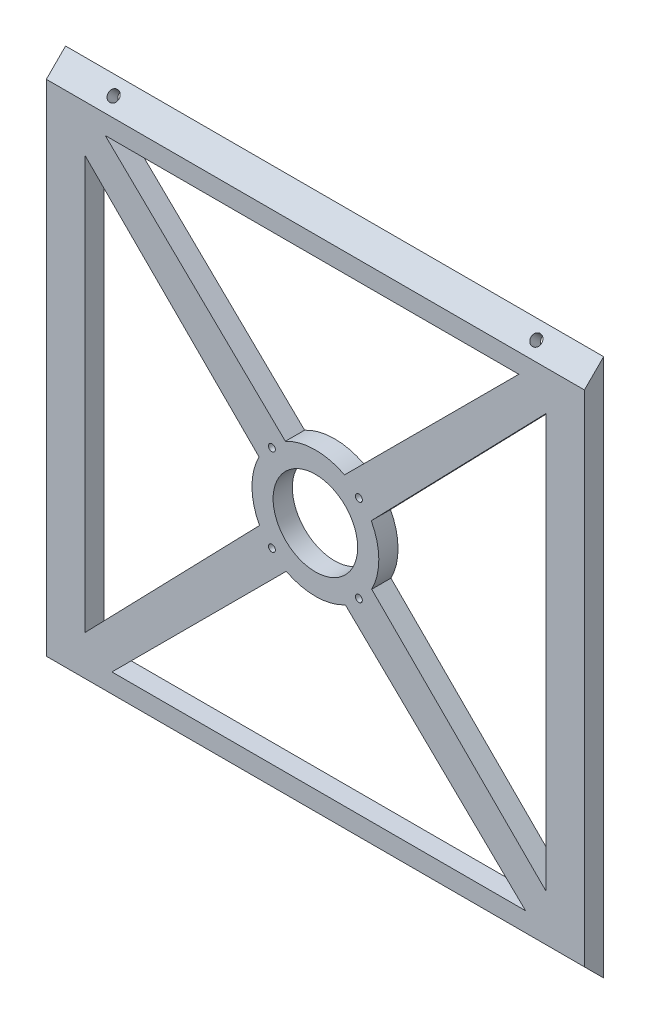
SolidWorks part; units mm, degrees
ref_plane "Front Plane" through (0, 0, 0) normal (0, 0, 1) x (1, 0, 0)
ref_plane "Top Plane" through (0, 0, 0) normal (0, 1, 0) x (1, 0, 0)
ref_plane "Right Plane" through (0, 0, 0) normal (1, 0, 0) x (0, 0, -1)
sketch "Sketch3" plane through (0, 0, 0) normal (0, 0, 1) x (1, 0, 0)
  line L1 (-70, 70) -> (70, 70)
  line L2 (-70, 70) -> (-70, -70)
  line L3 (-70, -70) -> (70, -70)
  line L4 (70, 70) -> (70, -70)
  line L5 (0, -70) -> (0, 70) construction
  line L6 (-70, 0) -> (70, 0) construction
  point P0 (0, 0)
  dimension "D1" = 140
  dimension "D2" = 140
extrude "Boss-Extrude1" add sketch "Sketch3" along normal blind 5
sketch "Sketch4" plane through (0, 0, 5) normal (0, 0, 1) x (1, 0, 0)
  line L0 (0, 0) -> (-70, 70) construction
  line L1 (0, 0) -> (70, 70) construction
  line L2 (-60, 60) -> (60, 60) construction
  line L3 (70, 70) -> (-70, 70) construction
  line L4 (-65, 70) -> (3.5355, 3.5355) construction
  line L5 (-3.5355, 3.5355) -> (52.9289, 60) construction
  line L6 (7.5831, 14.6542) -> (52.9289, 60)
  line L7 (-7.8076, 14.5359) -> (-54.6884, 60)
  line L8 (-54.6884, 60) -> (52.9289, 60)
  circle A0 centre (0, 0) radius 16.5 construction
  arc A1 (-7.8076, 14.5359) -> (7.5831, 14.6542) centre (0, 0) cw
  dimension "D1" = 33
  dimension "D2" = 10
  dimension "D3" = 10
  dimension "D4" = 5
  dimension "D5" = 5
  dimension "D6" = 5
extrude "Cut-Extrude1" cut sketch "Sketch4" against normal blind 5
pattern_circular "CirPattern1" count 4 over 360 about axis through (0, 0, 0) along (0, 0, 1) of "Cut-Extrude1"
sketch "Sketch7" plane through (0, 0, 5) normal (0, 0, 1) x (1, 0, 0)
  circle A0 centre (0, 0) radius 11
  dimension "D1" = 22
extrude "Cut-Extrude2" cut sketch "Sketch7" against normal up to next
sketch "Sketch8" plane through (0, 0, 5) normal (0, 0, 1) x (1, 0, 0)
  line L0 (0, 0) -> (70, -70) construction
  circle A0 centre (0, 0) radius 16 construction
  point P3 (11.3137, -11.3137)
  dimension "D1" = 32
hole_wizard "Ø1.8 (1.8) Diameter Hole1" positions "3DSketch3" profile "Sketch9" hole size "Ø1.8" standard "ANSI Metric"
sketch3d "3DSketch3"
  point P0 (11.3137, -11.3137, 5)
sketch "Sketch9" plane through (11.3137, -11.3137, 5) normal (1, 0, 0) x (0, -1, 0)
  line L0 (0, 0) -> (0, 6.5408)
  line L1 (0, 6.5408) -> (0.9, 6)
  line L2 (0.9, 6) -> (0.9, 0)
  line L5 (0.9, 0) -> (0, 0)
  line L10 (0, 6.5408) -> (-0.9, 6) construction
  line L11 (0, -6.35) -> (0, 107.95) construction
  dimension "Hole Dia." = 1.8
  dimension "Hole Depth" = 6
  dimension "Drill Angle" = 118
pattern_circular "CirPattern2" count 4 over 360 about axis through (0, 0, 0) along (0, 0, 1) of "Ø1.8 (1.8) Diameter Hole1"
chamfer "Chamfer1" distance 5 angle 45 2 edges at (0, 70, 5) (0, -70, 5)
hole_wizard "Ø3.0mm Dowel Hole1" positions "3DSketch5" profile "Sketch12" hole size "Ø3.0" standard "ANSI Metric"
sketch3d "3DSketch5"
  line L0 (-70, 70, 0) -> (-70, -70, 0) construction
  point P0 (-70, 63, 2.5)
  dimension "D1" = 2.5
  dimension "D2" = 63
sketch "Sketch12" plane through (-70, 63, 2.5) normal (0, 1, 0) x (0, 0, 1)
  line L0 (0, 0) -> (0, 10.8412)
  line L1 (0, 10.8412) -> (1.4, 10)
  line L2 (1.4, 10) -> (1.4, 0)
  line L5 (1.4, 0) -> (0, 0)
  line L10 (0, 10.8412) -> (-1.4, 10) construction
  line L11 (0, -6.35) -> (0, 107.95) construction
  dimension "Hole Dia." = 2.8
  dimension "Hole Depth" = 10
  dimension "Drill Angle" = 118
mirror "Mirror1" about plane through (0, 0, 0) normal (0, 1, 0) of "Ø3.0mm Dowel Hole1"
hole_wizard "Ø3.0mm Dowel Hole2" positions "3DSketch6" profile "Sketch13" hole size "Ø3.0" standard "ANSI Metric"
sketch3d "3DSketch6"
  line L0 (70, 70, 0) -> (-70, 70, 0) construction
  point P0 (55, 67.5, 2.5)
  point P5 (0, 0, 0)
  dimension "D1" = 3.5355
  dimension "D2" = 55
sketch "Sketch13" plane through (55, 67.5, 2.5) normal (1, 0, 0) x (0, -0.7071, 0.7071)
  line L0 (0, 0) -> (0, 10.8412)
  line L1 (0, 10.8412) -> (1.4, 10)
  line L2 (1.4, 10) -> (1.4, 0)
  line L5 (1.4, 0) -> (0, 0)
  line L10 (0, 10.8412) -> (-1.4, 10) construction
  line L11 (0, -6.35) -> (0, 107.95) construction
  dimension "Hole Dia." = 2.8
  dimension "Hole Depth" = 10
  dimension "Drill Angle" = 118
mirror "Mirror2" about plane through (0, 0, 0) normal (1, 0, 0) of "Ø3.0mm Dowel Hole2"
mirror "Mirror3" about plane through (0, 0, 0) normal (0, 1, 0) of "Mirror2", "Ø3.0mm Dowel Hole2"
